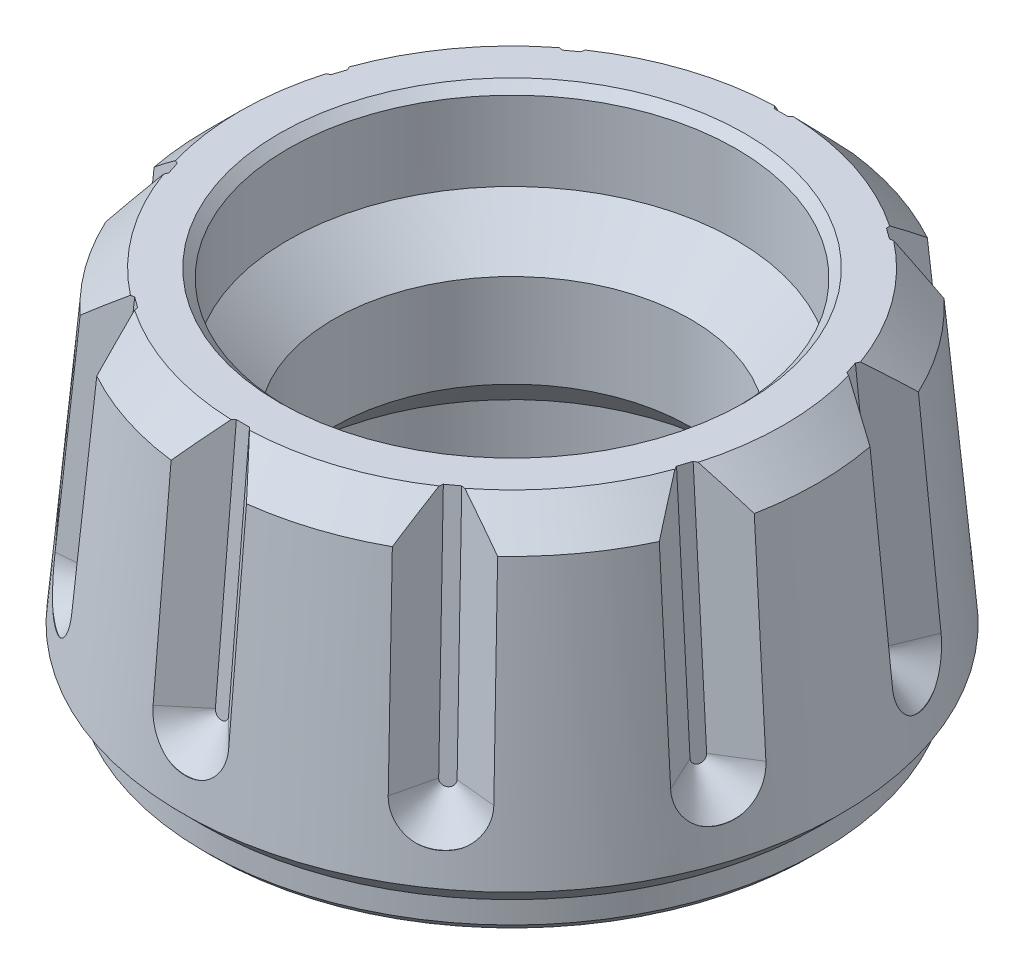
SolidWorks part; units mm, degrees
note: '?' marks a value the reader was unsure of.
ref_plane "前视基准面" through (0, 0, 0) normal (0, 0, 1) x (1, 0, 0)
ref_plane "上视基准面" through (0, 0, 0) normal (0, 1, 0) x (1, 0, 0)
ref_plane "右视基准面" through (0, 0, 0) normal (1, 0, 0) x (0, 0, -1)
sketch "草图1" plane through (0, 0, 0) normal (0, 0, 1) x (1, 0, 0)
  line L0 (6.8876, 8.2) -> (5.1, 8.2)
  line L3 (5.1, 8.2) -> (5.1, 6.2)
  line L4 (5.1, 0) -> (7, 0)
  line L5 (7, 0) -> (7, 0.7)
  line L6 (7, 0.7) -> (7.5437, 0.7) construction
  line L7 (7.5, 1.2) -> (6.8876, 8.2)
  line L9 (0, 0) -> (0, 23.3375) construction
  line L10 (7, 0.7) -> (7.9579, 1.6579) construction
  line L11 (7.5, 1.2) -> (8.3839, 1.2) construction
  line L12 (7, 0.7) -> (7.5, 1.2)
  line L13 (7.5, 1.2) -> (7.5437, 0.7) construction
  line L14 (5.1, 6.2) -> (3, 4.1)
  line L15 (3, 4.1) -> (5.1, 2)
  line L16 (5.1, 2) -> (5.1, 0)
  line L17 (5.1, 6.2) -> (5.1, 2) construction
  line L18 (3, 4.1) -> (5.1, 4.1) construction
  dimension "D1" = 8.2
  dimension "D2" = 2
  dimension "D3" = 5.1
  dimension "D4" = 1.2
  dimension "D5" = 0.7
  dimension "D7" = 5
  dimension "D8" = 7
  dimension "D9" = 45
  dimension "D10" = 7.5437
  dimension "D12" = 2
revolve "旋转1" add sketch "草图1" angle 360 about L9
chamfer "倒角4" distance 0.2 angle 45 1 edges at (0, 0, -7)
chamfer "倒角3" distance 0.7 angle 45 1 edges at (0, 8.2, -6.8876)
chamfer "倒角6" distance 0.2 angle 45 2 edges at (0, 0, -5.1) (0, 8.2, -5.1)
chamfer "倒角7" distance 1.5 angle 45 1 edges at (0, 4.1, -3)
ref_plane "基准面1" through (0, 0, 8.5) normal (0, 0, 1) x (1, 0, 0)
ref_axis "基准轴1" through (-8.3994, 0, 8.5) along (1, 0, 0)?
ref_plane "基准面2" through (0, 0.738, 8.4354) normal (0, 0.0872, 0.9962) x (1, 0, 0)
sketch "草图2" plane through (0, 0, 8.5) normal (0, 0.0872, 0.9962) x (1, 0, 0)
  line L0 (0, 0.7408) -> (0, 10.7408) construction
  line L1 (0, 10.1598) -> (0, 2.9) construction
  line L2 (0.9, 10.1598) -> (0.9, 2.9)
  line L3 (-0.9, 10.1598) -> (-0.9, 2.9)
  line L5 (-8.3994, 0) -> (8.3994, 0) construction
  arc A0 (0.9, 10.1598) -> (-0.9, 10.1598) centre (0, 10.1598) ccw
  arc A1 (-0.9, 2.9) -> (0.9, 2.9) centre (0, 2.9) ccw
  point P5 (0, 6.5299)
  dimension "D1" = 1.8
  dimension "D2" = 2.9
  dimension "D3" = 10
extrude "切除-拉伸1" cut sketch "草图2" against normal blind 1.652
ref_axis "基准轴2" through (0, 8, 0) along (0, -1, 0)?
chamfer "倒角5" distance 0.75 angle 45 8 edges at (0.0174, 1.9148, 7.4374) (0.9, 5.4711, 6.363) (0, 1.8484, 6.68) (-0.9, 5.4711, 6.363)
pattern_circular "阵列(圆周)1" count 10 over 360 about axis through (0, 0, 0) along (0, 1, 0) of "切除-拉伸1", "倒角5"
